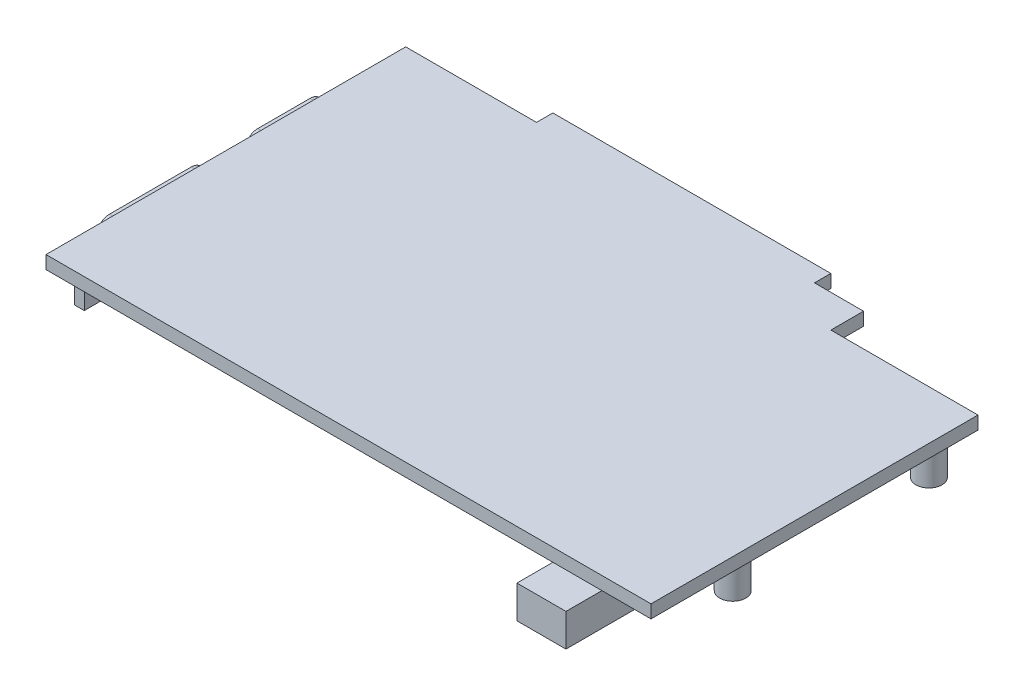
SolidWorks part; units mm, degrees
ref_plane "Front Plane" through (0, 0, 0) normal (0, 0, 1) x (1, 0, 0)
ref_plane "Top Plane" through (0, 0, 0) normal (0, 1, 0) x (1, 0, 0)
ref_plane "Right Plane" through (0, 0, 0) normal (1, 0, 0) x (0, 0, -1)
sketch "Sketch1" plane through (0, 0, 0) normal (0, 1, 0) x (1, 0, 0)
  line L1 (0, 0) -> (185, 0)
  line L2 (0, 0) -> (0, 100)
  line L3 (0, 100) -> (185, 100)
  line L4 (185, 0) -> (185, 100)
  dimension "D1" = 185
  dimension "D2" = 100
extrude "Boss-Extrude1" add sketch "Sketch1" along normal blind 4
sketch "Sketch2" plane through (0, 4, 0) normal (0, 1, 0) x (-1, 0, 0)
  line L0 (-185, -100) -> (0, -100) construction
  line L1 (-40, -100) -> (-125, -100)
  line L2 (-40, -100) -> (-40, -115)
  line L3 (-40, -115) -> (-125, -115)
  line L4 (-125, -100) -> (-125, -115)
  line L5 (-185, 0) -> (-185, -100) construction
  line L6 (-140, -100) -> (-140, -110)
  line L7 (0, -110) -> (-40, -110)
  line L8 (0, -100) -> (0, -110)
  line L9 (-140, -110) -> (-125, -110)
  line L10 (0, -100) -> (0, 0) construction
  line L11 (-185, 0) -> (-185, -100) construction
  line L12 (-185, -100) -> (0, -100) construction
  line M4 (-185, -100) -> (0, -100)
  dimension "D1" = 60
  dimension "D2" = 85
  dimension "D3" = 15
  dimension "D4" = 45
  dimension "D5" = 10
extrude "Boss-Extrude2" add sketch "Sketch2" against normal blind 4 contours L8 L2 M4 | L4 L3 L2 M4 | L6 L4 M4 region at (82.5, 4, -107.5) region at (20, 4, -105) region at (132.5, 4, -105)
sketch "Sketch3" plane through (0, 0, 0) normal (0, -1, 0) x (1, 0, 0)
  line L0 (0, 0) -> (185, 0) construction
  line L1 (1.6993, -110) -> (-8.3007, -110)
  line L2 (1.6993, -110) -> (1.6993, -10)
  line L3 (1.6993, -10) -> (-8.3007, -10)
  line L4 (-8.3007, -110) -> (-8.3007, -10)
  line L5 (0, -110) -> (40, -110) construction
  dimension "D1" = 10
  dimension "D2" = 10
extrude "Boss-Extrude3" add sketch "Sketch3" along normal blind 15
sketch "Sketch4" plane through (0, 0, 0) normal (0, -1, 0) x (1, 0, 0)
  line L0 (185, -100) -> (140, -100) construction
  line L1 (127.6293, -20) -> (147.6293, -20)
  line L2 (127.6293, -20) -> (127.6293, -90)
  line L3 (127.6293, -90) -> (147.6293, -90)
  line L4 (147.6293, -20) -> (147.6293, -90)
  line L5 (0, 0) -> (185, 0) construction
  dimension "D1" = 20
  dimension "D2" = 10
  dimension "D3" = 20
extrude "Boss-Extrude4" add sketch "Sketch4" along normal blind 6
sketch "Sketch5" plane through (0, 0, 0) normal (0, -1, 0) x (1, 0, 0)
  line L0 (0, 0) -> (185, 0) construction
  line L1 (170, 0) -> (155, 0)
  line L2 (170, 0) -> (170, -20)
  line L3 (170, -20) -> (155, -20)
  line L4 (155, 0) -> (155, -20)
  line L5 (185, 0) -> (185, -100) construction
  dimension "D1" = 15
  dimension "D2" = 20
  dimension "D3" = 15
extrude "Boss-Extrude5" add sketch "Sketch5" along normal blind 10
sketch "Sketch6" plane through (0, 0, 0) normal (0, -1, 0) x (1, 0, 0)
  line L0 (180, -1023.0016) -> (180, 48976.9984) construction
  line L1 (185, 0) -> (185, -100) construction
  line L2 (170, 0) -> (185, 0) construction
  circle A0 centre (180, -30) radius 4
  circle A1 centre (180, -90) radius 4
  dimension "D2" = 8
  dimension "D1" = 5
  dimension "D3" = 30
  dimension "D4" = 60
extrude "Boss-Extrude6" add sketch "Sketch6" along normal blind 10
sketch "Sketch7" plane through (-8.3007, 0, 0) normal (-1, 0, 0) x (0, 0, 1)
  line L0 (-27.7213, -7.3117) -> (-52.7213, -7.3117) construction
  line L1 (-27.7213, -11.3117) -> (-52.7213, -11.3117)
  line L2 (-27.7213, -3.3117) -> (-52.7213, -3.3117)
  line L3 (-73.0577, -7.3117) -> (-89.0577, -7.3117) construction
  line L4 (-73.0577, -11.3117) -> (-89.0577, -11.3117)
  line L5 (-73.0577, -3.3117) -> (-89.0577, -3.3117)
  arc A0 (-27.7213, -11.3117) -> (-27.7213, -3.3117) centre (-27.7213, -7.3117) ccw
  arc A1 (-52.7213, -3.3117) -> (-52.7213, -11.3117) centre (-52.7213, -7.3117) ccw
  arc A2 (-73.0577, -11.3117) -> (-73.0577, -3.3117) centre (-73.0577, -7.3117) ccw
  arc A3 (-89.0577, -3.3117) -> (-89.0577, -11.3117) centre (-89.0577, -7.3117) ccw
  point P2 (-40.2213, -7.3117)
  point P7 (-81.0577, -7.3117)
  dimension "D1" = 8
  dimension "D2" = 25
  dimension "D3" = 8
  dimension "D4" = 16
extrude "Cut-Extrude1" cut sketch "Sketch7" against normal blind 7 flip side to cut
sketch "Sketch8" plane through (-1.3007, 0, 0) normal (-1, 0, 0) x (0, 0, 1)
  line L0 (-24.2213, -7.3117) -> (-56.2213, -7.3117) construction
  line L1 (-68.8077, -7.3117) -> (-93.3077, -7.3117) construction
  line L2 (-40.2213, -7.3117) -> (-40.2213, -3.3117) construction
  line L5 (-27.7213, -3.3117) -> (-52.7213, -3.3117) construction
  line L6 (-40.2213, -7.3117) -> (-40.2213, -11.3117) construction
  line L7 (-52.7213, -11.3117) -> (-27.7213, -11.3117) construction
  line L8 (-81.0577, -3.3117) -> (-81.0577, -7.3117) construction
  line L9 (-73.0577, -3.3117) -> (-89.0577, -3.3117) construction
  line L10 (-81.0577, -7.3117) -> (-81.0577, -11.3117) construction
  line L11 (-89.0577, -11.3117) -> (-73.0577, -11.3117) construction
  circle A3 centre (-24.2213, -7.3117) radius 1.25
  circle A4 centre (-56.2213, -7.3117) radius 1.25
  circle A5 centre (-68.8077, -7.3117) radius 1.25
  circle A6 centre (-93.3077, -7.3117) radius 1.25
  dimension "D3" = 2.5
  dimension "D1" = 32
  dimension "D2" = 24.5
extrude "Cut-Extrude2" cut sketch "Sketch8" against normal blind 7 and the other way blind 7
sketch "Sketch9" plane through (0, 0, 0) normal (0, 0, 1) x (1, 0, 0)
  line L1 (155, -10) -> (170, -10)
  line L2 (155, -10) -> (155, 0)
  line L3 (155, 0) -> (170, 0)
  line L4 (170, -10) -> (170, 0)
extrude "Boss-Extrude7" add sketch "Sketch9" along normal blind 11
sketch "Sketch10" plane through (0, 0, 0) normal (0, -1, 0) x (1, 0, 0)
  line L0 (185, 0) -> (185, -100) construction
  line L1 (37, -22) -> (128, -22)
  line L2 (37, -22) -> (37, -95)
  line L3 (37, -95) -> (128, -95)
  line L4 (128, -22) -> (128, -95)
  line L5 (40, -115) -> (125, -115) construction
  dimension "D1" = 91
  dimension "D2" = 73
  dimension "D3" = 57
  dimension "D4" = 20
extrude "Boss-Extrude8" add sketch "Sketch10" along normal blind 18
